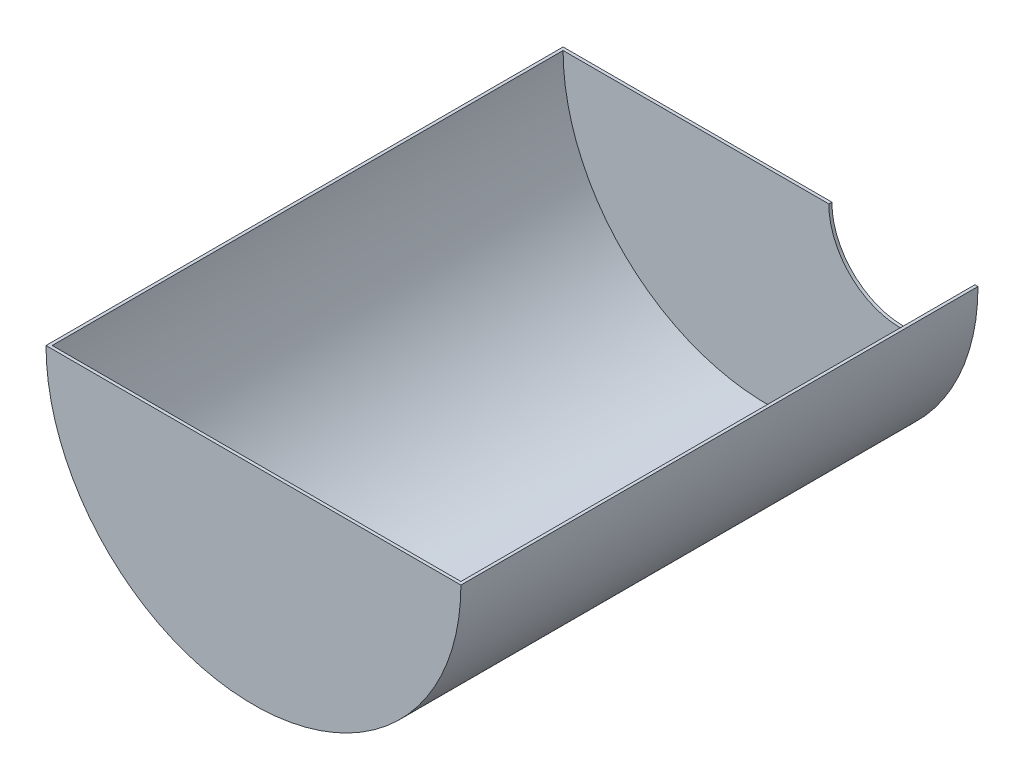
SolidWorks part; units mm, degrees
material "Cast Alloy Steel"
ref_plane "Front Plane" through (0, 0, 0) normal (0, 0, 1) x (1, 0, 0)
ref_plane "Top Plane" through (0, 0, 0) normal (0, 1, 0) x (1, 0, 0)
ref_plane "Right Plane" through (0, 0, 0) normal (1, 0, 0) x (0, 0, -1)
sketch "Sketch1" plane through (0, 0, 0) normal (0, 0, 1) x (1, 0, 0)
  line L1 (-200, 0) -> (200, 0)
  arc A0 (-200, 0) -> (200, 0) centre (0, 0) ccw
  dimension "D1" = 400
extrude "Boss-Extrude1" add sketch "Sketch1" along normal blind 500
shell "Shell1" thickness 3 removed face at (0, 0, 250) outward yes
sketch "Sketch2" plane through (0, 0, -3) normal (0, 0, -1) x (-1, 0, 0)
  line L0 (-203, 0) -> (203, 0) construction
  line L1 (-200, 0) -> (-60, 0)
  arc A0 (-200, 0) -> (-60, 0) centre (-130, 0) ccw
  point P1 (0, 0)
  dimension "D1" = 140
extrude "Cut-Extrude1" cut sketch "Sketch2" against normal blind 10
